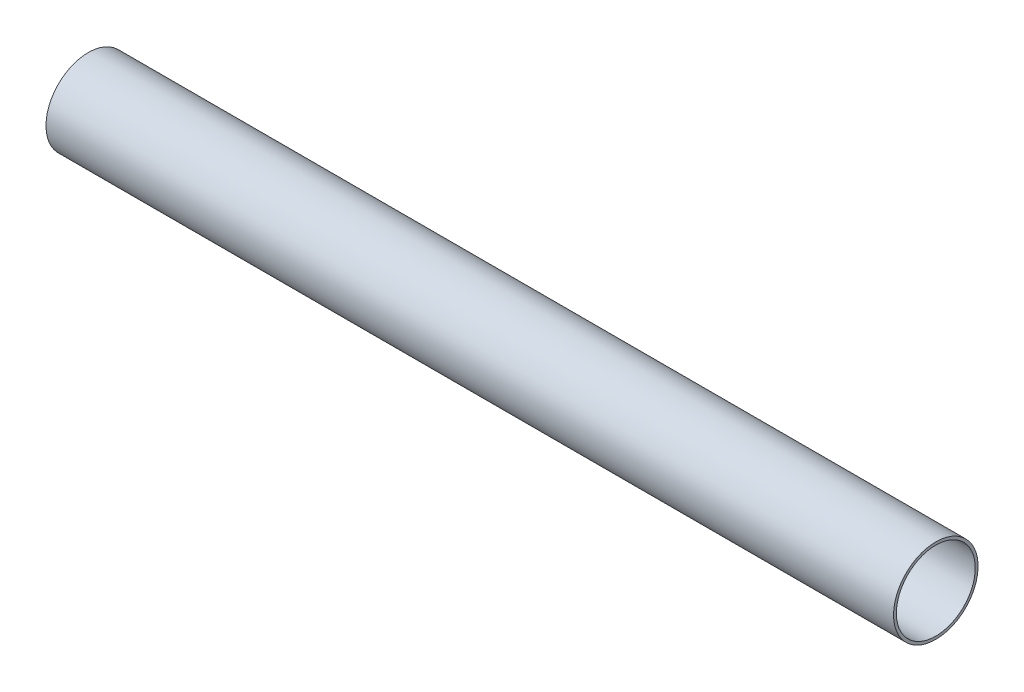
SolidWorks part; units mm, degrees
ref_plane "Plano frontal" through (0, 0, 0) normal (0, 0, 1) x (1, 0, 0)
ref_plane "Plano superior" through (0, 0, 0) normal (0, 1, 0) x (1, 0, 0)
ref_plane "Plano direito" through (0, 0, 0) normal (1, 0, 0) x (0, 0, -1)
sketch3d "3DSketch1"
  line L0 (-34220.2161, -17152.2928, 39207.3639) -> (-34520.9763, -17152.2928, 39207.3639)
  line L1 (-34220.2161, -16286.7026, 39207.3639) -> (-34220.2161, -17718.2109, 39207.3639) construction
  point P2 (0, 0, 0)
  point P3 (0, 0, 0)
  point P4 (0, 0, 0)
  point P5 (0, 0, 0)
  point P6 (0, 0, 0)
sweep "Sweep-Thin1" add path "3DSketch1" circular profile diameter 30 parameters "D1"=1, "D3"=30
